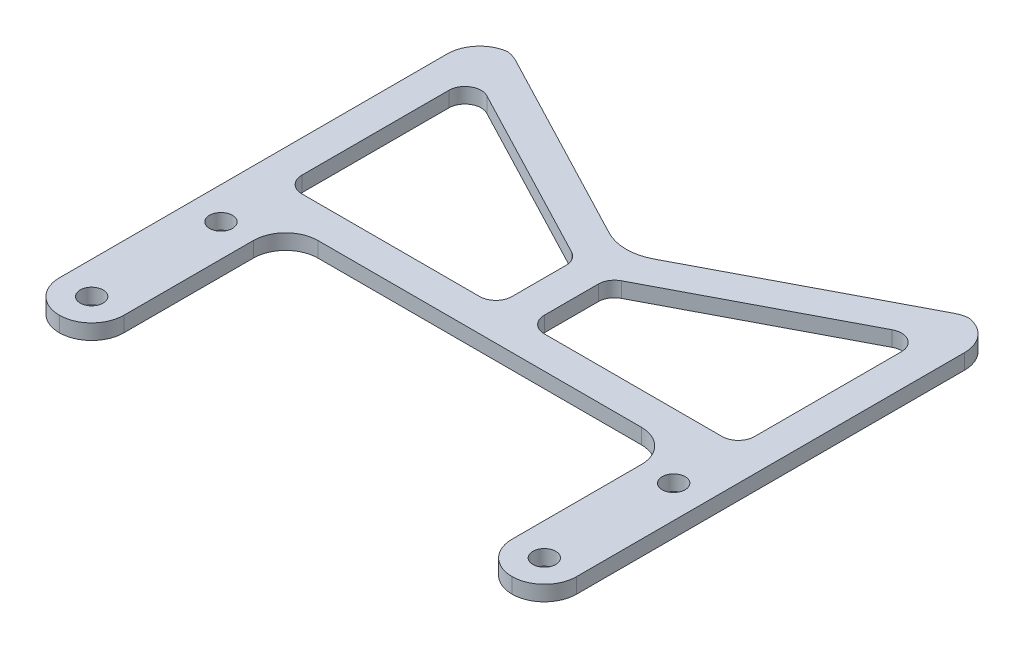
SolidWorks part; units mm, degrees
material "Custom Plastic"
ref_plane "Front Plane" through (0, 0, 0) normal (0, 0, 1) x (1, 0, 0)
ref_plane "Top Plane" through (0, 0, 0) normal (0, 1, 0) x (1, 0, 0)
ref_plane "Right Plane" through (0, 0, 0) normal (1, 0, 0) x (0, 0, -1)
sketch "Sketch1" plane through (0, 0, 0) normal (0, 1, 0) x (1, 0, 0)
  line L1 (-50.8, -44.45) -> (50.8, -44.45)
  line L2 (-50.8, -44.45) -> (-50.8, 44.45)
  line L3 (-50.8, 44.45) -> (50.8, 44.45)
  line L4 (50.8, -44.45) -> (50.8, 44.45)
  line L5 (-50.8, -44.45) -> (50.8, 44.45) construction
  line L6 (-50.8, 44.45) -> (50.8, -44.45) construction
  point P0 (0, 0)
  dimension "D1" = 101.6
  dimension "D2" = 88.9
extrude "Base" add sketch "Sketch1" along normal blind 2.9972
sketch "Sketch2" plane through (0, 2.9972, 0) normal (0, 1, 0) x (1, 0, 0)
  line L0 (-44.45, 44.45) -> (0, 21.2052)
  line L1 (50.8, 44.45) -> (-50.8, 44.45) construction
  line L2 (0, 21.2052) -> (44.45, 44.45)
  line L3 (-44.45, 44.45) -> (44.45, 44.45)
  line L4 (0, 0) -> (0, 44.45) construction
  circle A0 centre (0, 30.1625) radius 7.9375 construction
  dimension "D1" = 15.875
  dimension "D2" = 88.9
  dimension "D3" = 14.2875
extrude "Tube notch" cut sketch "Sketch2" against normal through all
sketch "Sketch3" plane through (0, 2.9972, 0) normal (0, 1, 0) x (1, 0, 0)
  line L1 (0, 0) -> (0, -44.45) construction
  line L2 (-44.45, -12.7) -> (44.45, -12.7) construction
  line L3 (-44.45, -12.7) -> (-44.45, -38.1) construction
  line L4 (-44.45, -38.1) -> (44.45, -38.1) construction
  line L5 (44.45, -12.7) -> (44.45, -38.1) construction
  line L6 (-50.8, -44.45) -> (50.8, -44.45) construction
  line L7 (-50.8, -6.35) -> (50.8, -6.35) construction
  line L8 (-50.8, 44.45) -> (-50.8, -44.45) construction
  line L9 (50.8, -44.45) -> (50.8, 44.45) construction
  point P9 (0, -12.7)
  dimension "D1" = 88.9
  dimension "D2" = 6.35
  dimension "D3" = 25.4
  dimension "D4" = 6.35
hole_wizard "Mounting holes" positions "Sketch5" profile "Sketch4" hole size "#8" standard "ANSI Inch" end condition through all
sketch "Sketch5" plane through (0, 2.9972, 0) normal (0, 1, 0) x (1, 0, 0)
  point P0 (-44.45, -12.7)
  point P3 (-44.45, -38.1)
  point P6 (44.45, -38.1)
  point P9 (44.45, -12.7)
sketch "Sketch4" plane through (-44.45, 2.9972, 12.7) normal (1, 0, 0) x (0, 0, 1)
  line L0 (0, 0) -> (0, 2.9972)
  line L1 (0, 2.9972) -> (2.2479, 2.9972)
  line L2 (2.2479, 2.9972) -> (2.2479, 0)
  line L5 (2.2479, 0) -> (0, 0)
  line L11 (0, -6.35) -> (0, 107.95) construction
  dimension "Thru Hole Dia." = 4.4958
  dimension "Thru Hole Depth" = 2.9972
sketch "Sketch8" plane through (0, 2.9972, 0) normal (0, 1, 0) x (1, 0, 0)
  line L0 (-50.8, -44.45) -> (50.8, -44.45) construction
  line L1 (-38.1, -44.45) -> (38.1, -44.45)
  line L2 (-38.1, -44.45) -> (-38.1, -6.35)
  line L3 (-38.1, -6.35) -> (38.1, -6.35)
  line L4 (38.1, -44.45) -> (38.1, -6.35)
  point P6 (0, -6.35)
  dimension "D1" = 38.1
  dimension "D2" = 76.2
extrude "Wheel cutout" cut sketch "Sketch8" against normal through all
fillet "Fillet1" radius 6.35 10 edges at (-50.8, 1.4986, 44.45) (-44.45, 1.4986, -44.45) (44.45, 1.4986, -44.45) (50.8, 1.4986, -44.45) (50.8, 1.4986, 44.45) (38.1, 1.4986, 44.45) (38.1, 1.4986, 6.35) (-38.1, 1.4986, 6.35) (-38.1, 1.4986, 44.45) (-50.8, 1.4986, -44.45)
fillet "Fillet2" radius 9.525 1 edges at (0, 1.4986, -21.2052)
sketch "Sketch9" plane through (0, 2.9972, 0) normal (0, 1, 0) x (1, 0, 0)
  line L0 (-44.45, 0) -> (-44.45, 37.2841)
  line L1 (-44.45, 37.2841) -> (-3.175, 15.6997)
  line L2 (3.175, 15.6997) -> (44.45, 37.2841)
  line L3 (44.45, 37.2841) -> (44.45, 0)
  line L4 (44.45, 0) -> (3.175, 0)
  line L5 (-43.0675, 43.727) -> (-4.4139, 23.5134) construction
  line L6 (-50.8, 38.1) -> (-50.8, -38.1) construction
  line L7 (31.75, -6.35) -> (-31.75, -6.35) construction
  line L8 (-3.175, 15.6997) -> (-3.175, 0)
  line L9 (3.175, 15.6997) -> (3.175, 0)
  line L10 (-3.175, 0) -> (-44.45, 0)
  line L11 (4.4139, 23.5134) -> (43.0675, 43.727) construction
  line L12 (50.8, -38.1) -> (50.8, 38.1) construction
  dimension "D1" = 6.35
  dimension "D2" = 6.35
  dimension "D3" = 6.35
  dimension "D4" = 6.35
  dimension "D5" = 6.35
extrude "Cut-Extrude1" cut sketch "Sketch9" against normal through all
fillet "Fillet3" radius 3.175 8 edges at (-44.45, 1.4986, 0) (-3.175, 1.4986, -15.6997) (-3.175, 1.4986, 0) (44.45, 1.4986, 0) (3.175, 1.4986, 0) (3.175, 1.4986, -15.6997) (44.45, 1.4986, -37.2841) (-44.45, 1.4986, -37.2841)
equation "\"MAT_THICKNESS\"=0.1"
